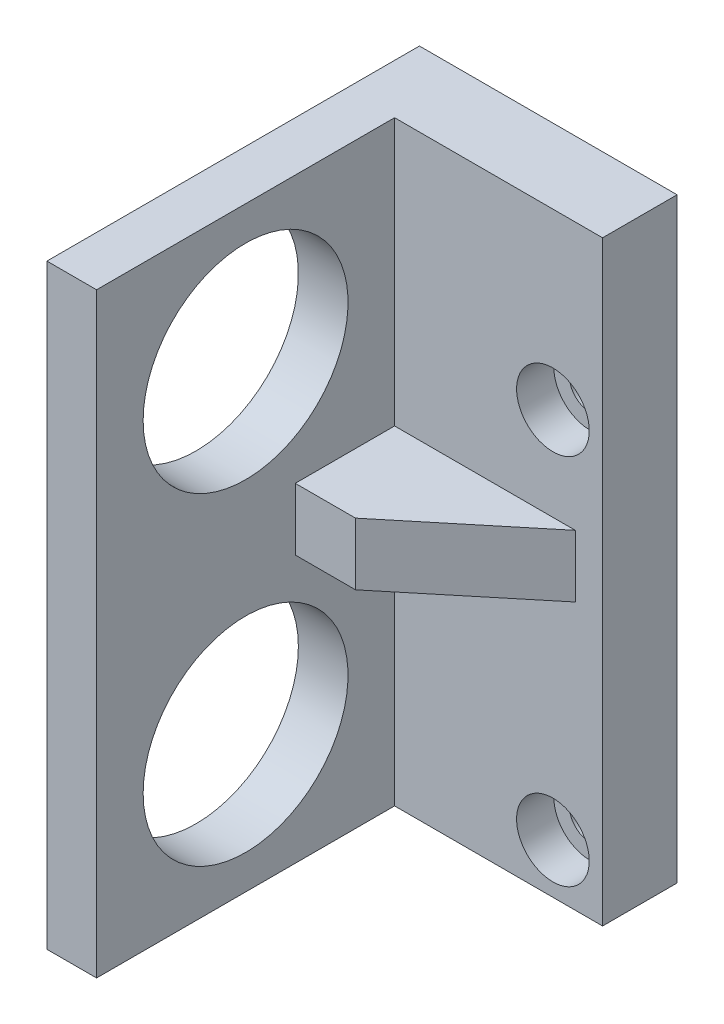
SolidWorks part; units mm, degrees
ref_plane "Front Plane" through (0, 0, 0) normal (0, 0, 1) x (1, 0, 0)
ref_plane "Top Plane" through (0, 0, 0) normal (0, 1, 0) x (1, 0, 0)
ref_plane "Right Plane" through (0, 0, 0) normal (1, 0, 0) x (0, 0, -1)
sketch "Sketch1" plane through (0, 0, 0) normal (0, 0, 1) x (1, 0, 0)
  line L0 (16.75, 48) -> (16.75, 0) construction
  line L1 (0, 0) -> (20.75, 0)
  line L2 (0, 0) -> (0, 48)
  line L3 (0, 48) -> (20.75, 48)
  line L4 (20.75, 0) -> (20.75, 48)
  circle A0 centre (16.75, 34) radius 1.675
  circle A1 centre (16.75, 4) radius 1.675
  dimension "D2" = 3.35
  dimension "D3" = 3.35
  dimension "D1" = 16.75
  dimension "D4" = 30
  dimension "D5" = 14
  dimension "D6" = 4
  dimension "D7" = 4
extrude "Boss-Extrude1" add sketch "Sketch1" along normal blind 6
sketch "Sketch2" plane through (0, 0, 0) normal (-1, 0, 0) x (0, 0, 1)
  line L1 (0, 48) -> (30, 48)
  line L2 (0, 48) -> (0, 0)
  line L3 (0, 0) -> (30, 0)
  line L4 (30, 48) -> (30, 0)
  dimension "D1" = 30
extrude "Boss-Extrude2" add sketch "Sketch2" against normal blind 4
sketch "Sketch3" plane through (0, 0, 0) normal (-1, 0, 0) x (0, 0, 1)
  line L0 (18, 48) -> (18, 0) construction
  line L1 (30, 48) -> (0, 48) construction
  line L2 (30, 0) -> (0, 0) construction
  line L3 (18, 24) -> (18.0919, 24) construction
  line L4 (0, 48) -> (0, 0) construction
  circle A0 centre (18, 37) radius 8.25
  circle A1 centre (18, 11) radius 8.25
  dimension "D1" = 16.5
  dimension "D2" = 13
  dimension "D3" = 18
extrude "Cut-Extrude1" cut sketch "Sketch3" against normal blind 6
sketch "Sketch4" plane through (0, 48, 0) normal (0, 1, 0) x (1, 0, 0)
  line L0 (4, -18) -> (4, -6)
  line L1 (4, -30) -> (4, -6) construction
  line L2 (4, -6) -> (18.5559, -6)
  line L3 (20.75, -6) -> (4, -6) construction
  line L4 (18.5559, -6) -> (4, -18)
extrude "Boss-Extrude3" add sketch "Sketch4" along normal blind 5 from offset 26.5 offset against normal yes
sketch "Sketch5" plane through (0, 0, 6) normal (0, 0, 1) x (1, 0, 0)
  circle A0 centre (16.75, 34) radius 2.925
  circle A1 centre (16.75, 4) radius 2.925
  dimension "D1" = 5.85
  dimension "D2" = 5.85
extrude "Cut-Extrude2" cut sketch "Sketch5" against normal blind 3
sketch "Sketch6" plane through (4, 0, 0) normal (1, 0, 0) x (0, 0, -1)
  line L0 (-6, 26.5) -> (-18, 26.5) construction
  line L1 (-18, 21.5) -> (-14, 21.5)
  line L2 (-18, 21.5) -> (-18, 26.5)
  line L3 (-18, 26.5) -> (-14, 26.5)
  line L4 (-14, 21.5) -> (-14, 26.5)
  dimension "D1" = 4
extrude "Cut-Extrude3" cut sketch "Sketch6" along normal blind 34
